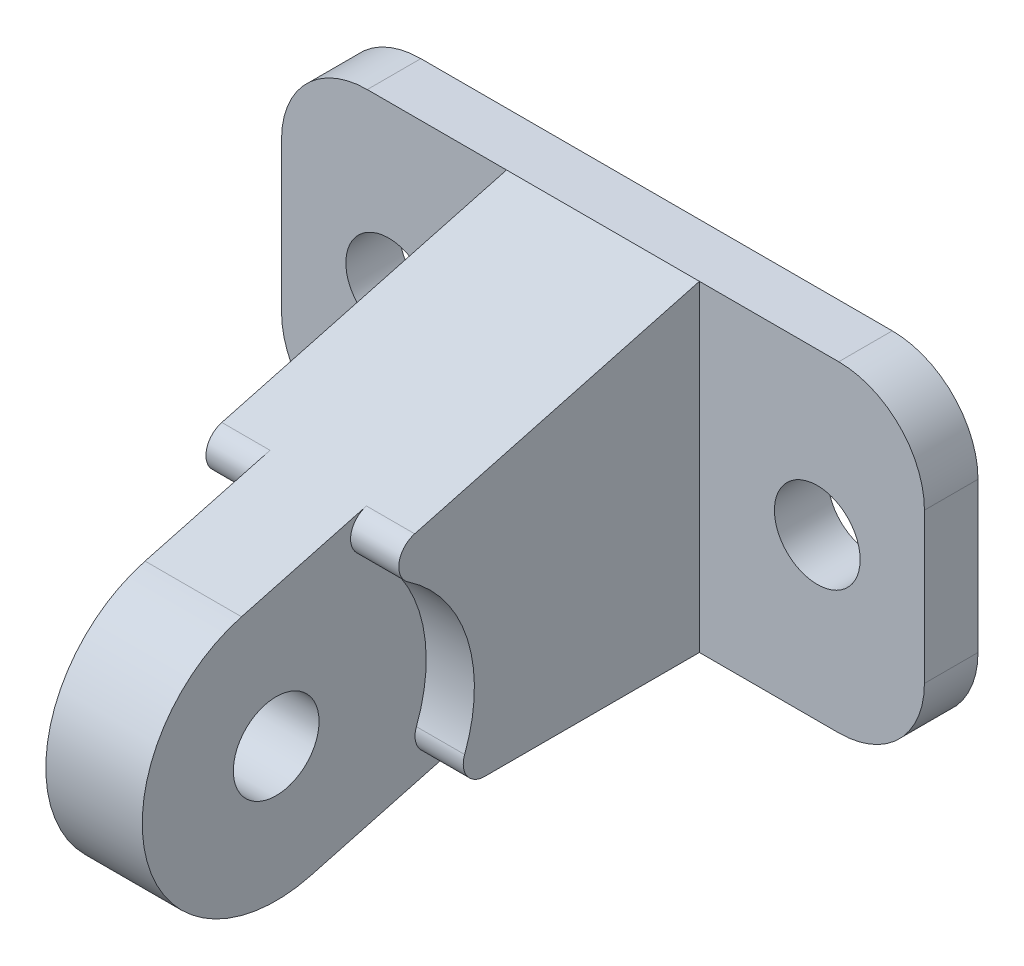
SolidWorks part; units mm, degrees
ref_plane "Front Plane" through (0, 0, 0) normal (0, 0, 1) x (1, 0, 0)
ref_plane "Top Plane" through (0, 0, 0) normal (0, 1, 0) x (1, 0, 0)
ref_plane "Right Plane" through (0, 0, 0) normal (1, 0, 0) x (0, 0, -1)
sketch "Sketch1" plane through (0, 0, 0) normal (0, 0, 1) x (1, 0, 0)
  line L0 (55, 0) -> (-55, 0) construction
  line L1 (22, -15) -> (-22, -15)
  line L2 (30, -7) -> (30, 7)
  line L3 (22, 15) -> (-22, 15)
  line L4 (-30, -7) -> (-30, 7)
  line L5 (30, -15) -> (-30, 15) construction
  line L6 (30, 15) -> (-30, -15) construction
  arc A0 (22, -15) -> (30, -7) centre (22, -7) ccw
  arc A1 (30, 7) -> (22, 15) centre (22, 7) ccw
  arc A2 (-30, 7) -> (-22, 15) centre (-22, 7) cw
  arc A3 (-22, -15) -> (-30, -7) centre (-22, -7) cw
  circle A4 centre (-20, 0) radius 4
  circle A5 centre (20, 0) radius 4
  point P0 (0, 0)
  dimension "D3" = 8
  dimension "D4" = 8
  dimension "D5" = 8
  dimension "D1" = 60
  dimension "D2" = 30
  dimension "D6" = 40
  dimension "D7" = 20
extrude "Boss-Extrude1" add sketch "Sketch1" along normal blind 5
sketch "Sketch2" plane through (0, 0, 0) normal (1, 0, 0) x (0, 0, -1)
  line L0 (-5, -15) -> (-25.0425, -15)
  line L1 (-5, 15) -> (-31.5739, 7.8795)
  line L2 (-5, -10.8819) -> (-36.7648, -19.3932)
  line L3 (0, 16.5) -> (0, -16.5) construction
  line L4 (-5, 15) -> (-5, -10.8819)
  line L5 (-5, 15) -> (-5, -15)
  line L7 (-5, 15) -> (-43.2352, 4.7549)
  arc A0 (-43.2352, 4.7549) -> (-36.7648, -19.3932) centre (-40, -7.3192) ccw
  arc A1 (-32.1742, 4.2893) -> (-26.9121, -12.2899) centre (-40, -7.3192) cw
  arc A2 (-26.9121, -12.2899) -> (-25.0425, -15) centre (-25.0425, -13) ccw
  arc A3 (-32.1742, 4.2893) -> (-31.5739, 7.8795) centre (-31.0563, 5.9477) cw
  circle A4 centre (-40, -7.3192) radius 4
  dimension "D2" = 25
  dimension "D3" = 14
  dimension "D4" = 2
  dimension "D5" = 8
  dimension "D1" = 40
extrude "Boss-Extrude2" add sketch "Sketch2" along normal mid plane 18 contours L5 L0 A2 A1 A3 L1
extrude "Boss-Extrude3" add sketch "Sketch2<3>" along normal mid plane 9 contours A1 A3 L7 A0 L2 L0 A2 A4 region at (0, -16.7869, 28.6766)
sketch "Sketch2<3>" plane through (0, 0, 0) normal (1, 0, 0) x (0, 0, -1) same geometry as "Sketch2"
